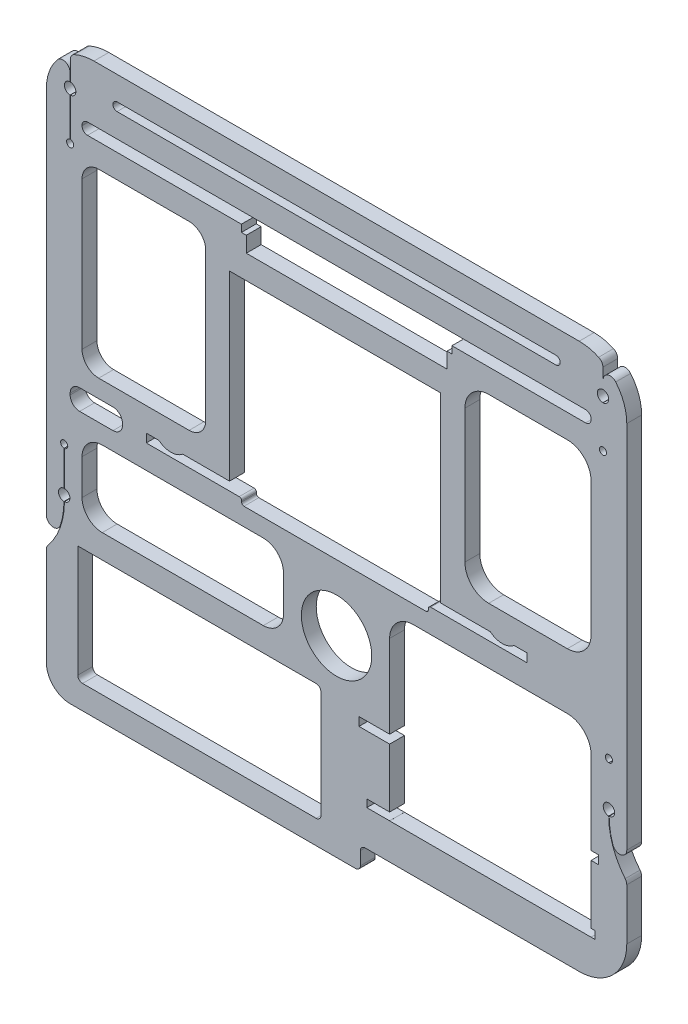
SolidWorks part; units mm, degrees
ref_plane "Front Plane" through (0, 0, 0) normal (0, 0, 1) x (1, 0, 0)
ref_plane "Top Plane" through (0, 0, 0) normal (0, 1, 0) x (1, 0, 0)
ref_plane "Right Plane" through (0, 0, 0) normal (1, 0, 0) x (0, 0, -1)
sketch "Sketch1" plane through (0, 0, 0) normal (0, 0, 1) x (1, 0, 0)
  line L0 (63.9883, 61.406) -> (63.9883, 57.596) construction
  line L1 (11.1776, 3.1158) -> (73.1542, 3.1158)
  line L2 (11.1776, 3.1158) -> (11.1776, 61.406)
  line L3 (11.1776, 61.406) -> (73.1542, 61.406)
  line L4 (73.1542, 3.1158) -> (73.1542, 61.406)
  line L5 (69.3442, 57.596) -> (14.9876, 57.596)
  line L6 (69.3442, 57.596) -> (69.3442, 6.9258)
  line L7 (69.3442, 6.9258) -> (14.9876, 6.9258)
  line L8 (14.9876, 57.596) -> (14.9876, 6.9258)
  line L9 (63.9883, 59.501) -> (18.0707, 59.501) construction
  line L10 (14.9876, 39.3805) -> (11.1776, 39.3805) construction
  line L11 (13.0826, 39.3805) -> (13.0826, 23.9527) construction
  line L12 (13.5248, 6.9258) -> (13.5248, 3.1158) construction
  line L13 (13.5248, 5.0208) -> (21.1598, 5.0208) construction
  line L14 (73.1542, 38.1916) -> (69.3442, 38.1916) construction
  line L15 (71.2492, 38.1916) -> (71.2492, 22.3321) construction
  line L16 (55.7422, 59.501) -> (30.5962, 59.501) construction
  line L19 (42.3087, 5.0208) -> (41.7626, 5.0208) construction
  line L21 (69.3442, 27.6227) -> (69.3442, 52.516) construction
  line L22 (14.9876, 47.563) -> (14.9876, 27.6227) construction
  dimension "D1" = 3.81
  dimension "D2" = 3.81
extrude "Boss-Extrude1" add sketch "Sketch1" along normal blind 1.5875
sketch "Sketch2" plane through (0, 0, 0) normal (0, 0, -1) x (-1, 0, 0)
  line L0 (-69.3442, 6.9258) -> (-69.3442, 57.596) construction
  line L1 (-69.3442, 28.8799) -> (-14.9876, 28.8799)
  line L2 (-69.3442, 28.8799) -> (-69.3442, 26.3399)
  line L3 (-69.3442, 26.3399) -> (-14.9876, 26.3399)
  line L4 (-14.9876, 28.8799) -> (-14.9876, 26.3399)
  line L5 (-14.9876, 57.596) -> (-14.9876, 6.9258) construction
  line L7 (-53.9642, 53.4304) -> (-53.9642, 51.7667)
  line L8 (-32.5266, 53.4304) -> (-32.0059, 53.4304)
  line L9 (-32.5266, 51.7667) -> (-53.9642, 51.7667) construction
  line L10 (-32.5266, 51.7667) -> (-32.5266, 53.4304) construction
  line L11 (-69.3442, 54.1924) -> (-54.4849, 54.1924)
  line L12 (-69.3442, 54.1924) -> (-69.3442, 51.6524)
  line L13 (-69.3442, 51.6524) -> (-55.8692, 51.6524)
  line L14 (-14.9876, 54.1924) -> (-14.9876, 51.6524)
  line L15 (-69.3442, 57.596) -> (-14.9876, 57.596)
  line L16 (-69.3442, 57.596) -> (-69.3442, 55.4243)
  line L17 (-69.3442, 55.4243) -> (-14.9876, 55.4243)
  line L18 (-14.9876, 57.596) -> (-14.9876, 55.4243)
  line L19 (-69.3442, 57.596) -> (-14.9876, 57.596) construction
  line L20 (-54.4849, 54.1924) -> (-54.4849, 53.4304)
  line L21 (-62.3462, 55.4243) -> (-23.9922, 55.4243) construction
  line L22 (-54.4849, 53.4304) -> (-53.9642, 53.4304)
  line L23 (-32.5266, 51.7667) -> (-53.9642, 51.7667)
  line L24 (-32.5266, 51.7667) -> (-32.5266, 53.4304)
  line L25 (-55.8692, 51.6524) -> (-55.8692, 49.2267)
  line L26 (-55.8692, 49.2267) -> (-30.6216, 49.2267)
  line L27 (-30.6216, 49.2267) -> (-30.6216, 51.6524)
  line L28 (-30.6216, 51.6524) -> (-14.9876, 51.6524)
  line L29 (-32.0059, 53.4304) -> (-32.0059, 54.1924)
  line L30 (-62.3462, 54.1924) -> (-23.9922, 54.1924) construction
  line L31 (-62.4859, 28.8799) -> (-21.8459, 28.8799) construction
  line L32 (-54.4849, 53.4304) -> (-54.4849, 54.1924) construction
  line L33 (-32.0059, 53.4304) -> (-54.4849, 53.4304) construction
  line L34 (-32.0059, 54.1924) -> (-14.9876, 54.1924)
  line L36 (-32.0059, 53.4304) -> (-32.0059, 54.1924) construction
  line L37 (-32.5266, 51.7667) -> (-32.5266, 53.4304) construction
  dimension "D1" = 2.54
  dimension "D2" = 1.905
  dimension "D3" = 2.54
  dimension "D4" = 1.905
  dimension "D5" = 2.54
extrude "Boss-Extrude2" add sketch "Sketch2" against normal up to surface (1.5875 mm away) up to face at (42.1659, 32.2609, 1.5875)
sketch "Sketch3" plane through (0, 0, 0) normal (0, 0, -1) x (-1, 0, 0)
  line L1 (-51.983, 32.3343) -> (-51.983, 29.7943) construction
  line L2 (-53.253, 29.7943) -> (-69.3442, 29.7943)
  line L3 (-69.3442, 28.8799) -> (-69.3442, 51.6524) construction
  line L4 (-69.3442, 29.7943) -> (-69.3442, 32.3343)
  line L5 (-69.3442, 32.3343) -> (-55.8692, 32.3343)
  line L7 (-53.253, 29.7943) -> (-53.253, 49.2267)
  line L8 (-55.8692, 49.2267) -> (-30.6216, 49.2267) construction
  line L9 (-53.253, 49.2267) -> (-55.8692, 49.2267)
  line L10 (-55.8692, 49.2267) -> (-55.8692, 32.3343)
  line L12 (-62.4859, 29.7943) -> (-21.8459, 29.7943) construction
  line L13 (-30.7359, 29.7943) -> (-14.9876, 29.7943)
  line L14 (-14.9876, 51.6524) -> (-14.9876, 28.8799) construction
  line L15 (-14.9876, 29.7943) -> (-14.9876, 32.3343)
  line L16 (-14.9876, 32.3343) -> (-28.1959, 32.3343)
  line L17 (-28.1959, 32.3343) -> (-28.1959, 51.6524)
  line L18 (-30.6216, 51.6524) -> (-14.9876, 51.6524) construction
  line L19 (-28.1959, 51.6524) -> (-30.7359, 51.6524)
  line L20 (-30.7359, 51.6524) -> (-30.7359, 29.7943)
  line L21 (-32.0059, 32.3343) -> (-32.0059, 29.7943) construction
  line L22 (-55.8692, 51.6524) -> (-55.8692, 49.2267) construction
  line M22 (-69.3442, 28.8799) -> (-69.3442, 51.6524)
  line M25 (-55.8692, 49.2267) -> (-30.6216, 49.2267)
  line M27 (-30.6216, 51.6524) -> (-14.9876, 51.6524)
  line M28 (-14.9876, 51.6524) -> (-14.9876, 28.8799)
  dimension "D1" = 2.54
  dimension "D3" = 2.54
  dimension "D4" = 2.54
  dimension "D5" = 1.27
  dimension "D6" = 1.27
extrude "Boss-Extrude3" add sketch "Sketch3" against normal up to surface (1.5875 mm away) contours L10 L5 L2 L7 M25 M22 | L20 L13 L16 L17 M27 M28 region at (30.4665, 50.4396, 0) region at (61.2986, 30.0466, 0) up to face at (42.8855, 53.7395, 1.5875)
sketch "Sketch4" plane through (0, 0, 0) normal (0, 0, -1) x (-1, 0, 0)
  line L0 (-69.3442, 26.3399) -> (-14.9876, 26.3399) construction
  line L1 (-47.8301, 26.3399) -> (-36.5017, 26.3399)
  line L2 (-47.8301, 26.3399) -> (-47.8301, 6.9258)
  line L3 (-47.8301, 6.9258) -> (-36.5017, 6.9258)
  line L4 (-36.5017, 26.3399) -> (-36.5017, 6.9258)
  line L5 (-14.9876, 6.9258) -> (-69.3442, 6.9258) construction
  line L6 (-45.9251, 21.2246) -> (-47.8301, 21.2246) construction
  line L7 (-38.4067, 21.2246) -> (-36.5017, 21.2246) construction
  circle A0 centre (-42.1659, 21.2246) radius 3.7592 construction
  dimension "D1" = 1.905
extrude "Boss-Extrude4" add sketch "Sketch4" against normal up to surface (1.5875 mm away) up to face at (21.5917, 41.9934, 1.5875)
sketch "Sketch5" plane through (0, 0, 0) normal (0, 0, -1) x (-1, 0, 0)
  line L0 (-14.5338, 15.7015) -> (-40.4926, 15.7015) construction
  line L3 (-40.4926, 3.2428) -> (-40.4926, 15.7015) construction
  line L4 (-14.5338, 3.2428) -> (-40.4926, 3.2428) construction
  line L5 (-14.5338, 3.2428) -> (-14.5338, 15.7015) construction
  line L6 (-14.5338, 15.7015) -> (-40.4926, 15.7015)
  line L7 (-40.4926, 3.2428) -> (-40.4926, 15.7015)
  line L8 (-14.5338, 3.2428) -> (-40.4926, 3.2428)
  line L9 (-14.5338, 3.2428) -> (-14.5338, 15.7015)
  circle A0 centre (-42.1659, 21.2246) radius 3.7592 construction
  circle A1 centre (-42.1659, 21.2246) radius 3.7592
extrude "Cut-Extrude1" cut sketch "Sketch5" against normal up to surface (1.5875 mm away) up to face at (58.5871, 16.6329, 1.5875)
sketch "Sketch8" plane through (0, 0, 0) normal (0, 0, -1) x (-1, 0, 0)
  line L1 (-36.5017, 15.7015) -> (-14.9876, 15.7015)
  line L2 (-36.5017, 15.7015) -> (-36.5017, 18.2415)
  line L3 (-36.5017, 18.2415) -> (-14.9876, 18.2415)
  line L4 (-14.9876, 15.7015) -> (-14.9876, 18.2415)
  line L5 (-14.9876, 26.3399) -> (-14.9876, 15.7015) construction
  dimension "D1" = 2.54
extrude "Boss-Extrude5" add sketch "Sketch8" against normal up to surface (1.5875 mm away) up to face at (38.4067, 21.2246, 1.5875)
fillet "Fillet1" radius 5.08 3 edges at (73.1542, 3.1158, 0.7937) (11.1776, 61.406, 0.7937) (73.1542, 61.406, 0.7937)
fillet "Fillet2" radius 2.54 4 edges at (69.3442, 51.6524, 0.7937) (55.8692, 32.3343, 0.7937) (69.3442, 32.3343, 0.7937) (55.8692, 51.6524, 0.7937)
fillet "Fillet3" radius 1.778 4 edges at (14.9876, 32.3343, 0.7937) (28.1959, 32.3343, 0.7937) (14.9876, 51.6524, 0.7937) (28.1959, 51.6524, 0.7937)
fillet "Fillet4" radius 0.5842 4 edges at (14.9876, 55.4243, 0.7937) (69.3442, 55.4243, 0.7937) (69.3442, 54.1924, 0.7937) (14.9876, 54.1924, 0.7937)
fillet "Fillet8" radius 2.159 4 edges at (36.5017, 18.2415, 0.7937) (36.5017, 26.3399, 0.7937) (14.9876, 26.3399, 0.7937) (14.9876, 18.2415, 0.7937)
sketch "Sketch6" plane through (0, 0, 0) normal (0, 0, -1) x (-1, 0, 0)
  circle A0 centre (-71.2492, 19.6852) radius 0.6096 construction
  circle A1 centre (-71.2492, 19.6852) radius 0.6096
  circle A4 centre (-70.6142, 57.596) radius 0.6096 construction
  circle A5 centre (-70.6142, 57.596) radius 0.6096
  circle A6 centre (-13.0826, 19.6852) radius 0.6096 construction
  circle A7 centre (-13.0826, 19.6852) radius 0.6096
  circle A10 centre (-13.7176, 57.596) radius 0.6096 construction
  circle A11 centre (-13.7176, 57.596) radius 0.6096
extrude "Cut-Extrude2" cut sketch "Sketch6" against normal up to surface (1.5875 mm away) up to face at (27.5132, 9.4722, 1.5875)
sketch "Sketch7" plane through (0, 0, 0) normal (0, 0, -1) x (-1, 0, 0)
  line L0 (-44.5566, 14.9395) -> (-70.1344, 14.9395) construction
  line L1 (-70.1344, 14.9395) -> (-70.1344, 14.0251) construction
  line L2 (-70.1344, 14.0251) -> (-44.5566, 14.0251) construction
  line L3 (-44.5566, 14.0251) -> (-44.5566, 14.9395) construction
  line L4 (-45.3906, 7.7431) -> (-69.7746, 7.7431) construction
  line L5 (-69.7746, 7.7431) -> (-69.7746, 6.9303) construction
  line L6 (-69.7746, 6.9303) -> (-45.3906, 6.9303) construction
  line L7 (-45.3906, 6.9303) -> (-45.3906, 7.7431) construction
  line L8 (-44.5566, 14.9395) -> (-70.1344, 14.9395)
  line L9 (-70.1344, 14.9395) -> (-70.1344, 14.0251)
  line L10 (-70.1344, 14.0251) -> (-44.5566, 14.0251)
  line L11 (-44.5566, 14.0251) -> (-44.5566, 14.9395)
  line L12 (-45.3906, 7.7431) -> (-69.7746, 7.7431)
  line L13 (-69.7746, 7.7431) -> (-69.7746, 6.9303)
  line L14 (-69.7746, 6.9303) -> (-45.3906, 6.9303)
  line L15 (-45.3906, 6.9303) -> (-45.3906, 7.7431)
  line L20 (-67.1076, 7.7431) -> (-48.0576, 7.7431)
  line L21 (-48.0576, 7.7431) -> (-48.0576, 9.6227)
  line L22 (-48.0576, 9.6227) -> (-67.1076, 9.6227)
  line L23 (-67.1076, 9.6227) -> (-67.1076, 7.7431)
  line L24 (-67.1076, 7.7431) -> (-48.0576, 7.7431)
  line L25 (-48.0576, 7.7431) -> (-48.0576, 9.6227)
  line L26 (-48.0576, 9.6227) -> (-67.1076, 9.6227)
  line L27 (-67.1076, 9.6227) -> (-67.1076, 7.7431)
  dimension "D1" = 0
extrude "Cut-Extrude3" cut sketch "Sketch7" against normal up to surface (1.5875 mm away) contours L14 L15 L12 L13 | L26 L27 L12 L25 | L10 L11 L8 L9 region at (57.3455, 14.4823, 0) region at (57.5826, 7.3367, 0) region at (57.5826, 8.6829, 0) up to face at (13.108, 57.596, 1.5875)
fillet "Fillet6" radius 0.508 3 edges at (40.4926, 15.7015, 0.7937) (40.4926, 3.2428, 0.7937) (14.5338, 3.2428, 0.7937)
sketch "Sketch9" plane through (0, 0, 1.5875) normal (0, 0, 1) x (1, 0, 0)
  line L0 (68.0742, 61.406) -> (16.2576, 61.406) construction
  line L1 (18.2896, 58.866) -> (66.0422, 58.866)
  line L2 (18.2896, 58.866) -> (18.2896, 57.9643)
  line L3 (18.2896, 57.9643) -> (66.0422, 57.9643)
  line L8 (66.0422, 58.866) -> (66.0422, 57.9643)
  line L9 (15.5718, 55.4243) -> (68.76, 55.4243) construction
  line L10 (11.1776, 56.326) -> (11.1776, 59.3208) construction
  line L11 (18.2896, 58.866) -> (11.1776, 58.866) construction
  line L13 (66.0422, 58.866) -> (73.1542, 58.866) construction
  line L14 (73.1542, 56.326) -> (73.1542, 56.8419) construction
  dimension "D1" = 2.54
  dimension "D2" = 2.54
  dimension "D3" = 7.112
extrude "Cut-Extrude4" cut sketch "Sketch9" against normal up to surface (1.5875 mm away) up to face at (58.1379, 12.0542, 0)
fillet "Fillet7" radius 0.4318 4 edges at (18.2896, 57.9643, 0.7937) (18.2896, 58.866, 0.7937) (66.0422, 57.9643, 0.7937) (66.0422, 58.866, 0.7937)
fillet "Fillet9" radius 2.54 2 edges at (69.3442, 26.3399, 0.7937) (47.8301, 26.3399, 0.7937)
sketch "Sketch10" plane through (0, 0, 1.5875) normal (0, 0, 1) x (1, 0, 0)
  line L0 (42.1659, 24.9838) -> (42.1659, -13.4858) construction
  line L1 (11.1776, 3.1158) -> (44.7059, 3.1158)
  line L2 (11.1776, 3.1158) -> (11.1776, 0.7028)
  line L3 (11.1776, 0.7028) -> (44.7059, 0.7028)
  line L4 (44.7059, 3.1158) -> (44.7059, 0.7028)
  line L5 (15.0418, 3.2428) -> (39.9846, 3.2428) construction
  circle A0 centre (42.1659, 21.2246) radius 3.7592 construction
  dimension "D1" = 2.54
  dimension "D2" = 2.54
extrude "Boss-Extrude6" add sketch "Sketch10" against normal up to surface (1.5875 mm away) up to face at (42.1659, 58.4152, 0)
fillet "Fillet10" radius 2.54 1 edges at (11.1776, 0.7028, 0.7937)
fillet "Fillet11" radius 0.508 2 edges at (44.7059, 3.1158, 0.7937) (44.7059, 0.7028, 0.7937)
sketch "Sketch11" plane through (0, 0, 1.5875) normal (0, 0, 1) x (1, 0, 0)
  line L0 (13.7049, 59.0933) -> (13.7049, 58.2055) construction
  line L1 (13.7049, 56.9866) -> (13.7049, 52.8968) construction
  line L2 (13.7303, 52.8968) -> (13.7303, 56.9866) construction
  line L3 (13.7303, 58.2055) -> (13.7303, 60.2667) construction
  line L4 (70.6015, 58.2055) -> (70.6015, 60.2667) construction
  line L5 (70.6269, 56.9866) -> (70.6269, 52.8968) construction
  line L6 (70.6015, 52.8968) -> (70.6015, 56.9866) construction
  line L7 (71.2619, 24.0038) -> (71.2619, 20.2947) construction
  line L8 (71.2365, 24.0038) -> (71.2365, 20.2947) construction
  line L9 (13.0953, 24.0038) -> (13.0953, 20.2947) construction
  line L10 (13.0699, 24.0038) -> (13.0699, 20.2947) construction
  line L11 (13.7049, 59.0933) -> (13.7049, 58.2055)
  line L12 (13.7049, 56.9866) -> (13.7049, 52.8968)
  line L13 (13.7303, 52.8968) -> (13.7303, 56.9866)
  line L14 (13.7303, 58.2055) -> (13.7303, 60.2667)
  line L15 (70.6015, 58.2055) -> (70.6015, 60.2667)
  line L16 (70.6269, 56.9866) -> (70.6269, 52.8968)
  line L17 (70.6015, 52.8968) -> (70.6015, 56.9866)
  line L18 (71.2619, 24.0038) -> (71.2619, 20.2947)
  line L19 (71.2365, 24.0038) -> (71.2365, 20.2947)
  line L20 (13.0953, 24.0038) -> (13.0953, 20.2947)
  line L21 (13.0699, 24.0038) -> (13.0699, 20.2947)
  line L22 (73.1542, 8.1958) -> (73.1542, 56.326) construction
  line L23 (11.1776, 56.326) -> (11.1776, 3.2428) construction
  line L24 (73.1542, 13.6774) -> (73.1542, 16.8829)
  line L25 (11.1776, 16.8829) -> (11.1776, 13.6774)
  line L26 (70.6269, 59.0933) -> (70.6269, 58.2055) construction
  line L27 (70.6269, 59.0933) -> (70.6269, 58.2055)
  arc A0 (13.7049, 59.0933) -> (12.3579, 59.5817) centre (12.9429, 59.0933) ccw construction
  arc A1 (13.7049, 52.8968) -> (13.7303, 52.8968) centre (13.7176, 52.516) ccw construction
  arc A2 (14.1807, 60.9621) -> (13.7303, 60.2667) centre (14.4923, 60.2667) ccw construction
  arc A3 (70.6015, 60.2667) -> (70.151, 60.9621) centre (69.8395, 60.2667) ccw construction
  arc A4 (71.9738, 59.5817) -> (70.6269, 59.0933) centre (71.3889, 59.0933) ccw construction
  arc A5 (70.6015, 52.8968) -> (70.6269, 52.8968) centre (70.6142, 52.516) ccw construction
  arc A6 (71.2619, 24.0038) -> (71.2365, 24.0038) centre (71.2492, 24.3846) ccw construction
  arc A7 (71.2746, 19.0762) -> (71.6692, 16.6421) centre (78.975, 19.0756) ccw construction
  arc A8 (71.6692, 16.6421) -> (73.1542, 16.8829) centre (72.3922, 16.8829) ccw construction
  arc A9 (71.2238, 19.0762) -> (72.9814, 14.1605) centre (78.975, 19.0756) ccw construction
  arc A10 (73.1542, 13.6774) -> (72.9814, 14.1605) centre (72.3922, 13.6774) ccw construction
  arc A11 (13.0953, 24.0038) -> (13.0699, 24.0038) centre (13.0826, 24.3846) ccw construction
  arc A12 (11.3503, 14.1605) -> (13.108, 19.0762) centre (5.3567, 19.0756) ccw construction
  arc A13 (12.6625, 16.6421) -> (13.0572, 19.0762) centre (5.3567, 19.0756) ccw construction
  arc A14 (11.1776, 16.8829) -> (12.6625, 16.6421) centre (11.9396, 16.8829) ccw construction
  arc A15 (11.3503, 14.1605) -> (11.1776, 13.6774) centre (11.9396, 13.6774) ccw construction
  arc A16 (13.7049, 59.0933) -> (12.3579, 59.5817) centre (12.9429, 59.0933) ccw
  arc A17 (13.7049, 52.8968) -> (13.7303, 52.8968) centre (13.7176, 52.516) ccw
  arc A18 (14.1807, 60.9621) -> (13.7303, 60.2667) centre (14.4923, 60.2667) ccw
  arc A19 (70.6015, 60.2667) -> (70.151, 60.9621) centre (69.8395, 60.2667) ccw
  arc A20 (71.9738, 59.5817) -> (70.6269, 59.0933) centre (71.3889, 59.0933) ccw
  arc A21 (70.6015, 52.8968) -> (70.6269, 52.8968) centre (70.6142, 52.516) ccw
  arc A22 (71.2619, 24.0038) -> (71.2365, 24.0038) centre (71.2492, 24.3846) ccw
  arc A23 (71.2746, 19.0762) -> (71.6692, 16.6421) centre (78.975, 19.0756) ccw
  arc A24 (71.6692, 16.6421) -> (73.1542, 16.8829) centre (72.3922, 16.8829) ccw
  arc A25 (71.2238, 19.0762) -> (72.9814, 14.1605) centre (78.975, 19.0756) ccw
  arc A26 (73.1542, 13.6774) -> (72.9814, 14.1605) centre (72.3922, 13.6774) ccw
  arc A27 (13.0953, 24.0038) -> (13.0699, 24.0038) centre (13.0826, 24.3846) ccw
  arc A28 (11.3503, 14.1605) -> (13.108, 19.0762) centre (5.3567, 19.0756) ccw
  arc A29 (12.6625, 16.6421) -> (13.0572, 19.0762) centre (5.3567, 19.0756) ccw
  arc A30 (11.1776, 16.8829) -> (12.6625, 16.6421) centre (11.9396, 16.8829) ccw
  arc A31 (11.3503, 14.1605) -> (11.1776, 13.6774) centre (11.9396, 13.6774) ccw
  arc A32 (16.2576, 61.406) -> (11.1776, 56.326) centre (16.2576, 56.326) ccw construction
  circle A33 centre (13.7176, 57.596) radius 0.6096 construction
  arc A34 (73.1542, 56.326) -> (68.0742, 61.406) centre (68.0742, 56.326) ccw construction
  circle A35 centre (70.6142, 57.596) radius 0.6096 construction
  circle A36 centre (71.2492, 19.6852) radius 0.6096 construction
  circle A37 centre (13.0826, 19.6852) radius 0.6096 construction
  arc A38 (14.1807, 60.9621) -> (12.3579, 59.5817) centre (16.2576, 56.326) ccw
  arc A39 (13.7303, 58.2055) -> (13.7049, 58.2055) centre (13.7176, 57.596) ccw
  arc A40 (71.9738, 59.5817) -> (70.151, 60.9621) centre (68.0742, 56.326) ccw
  arc A41 (70.6015, 56.9866) -> (70.6269, 56.9866) centre (70.6142, 57.596) ccw
  arc A42 (71.2619, 20.2947) -> (71.2365, 20.2947) centre (71.2492, 19.6852) ccw
  arc A43 (13.0572, 19.0762) -> (13.108, 19.0762) centre (13.0826, 19.6852) ccw
  arc A44 (13.0953, 20.2947) -> (13.0699, 20.2947) centre (13.0826, 19.6852) ccw
  arc A45 (13.7049, 56.9866) -> (13.7303, 56.9866) centre (13.7176, 57.596) ccw
  arc A46 (71.2238, 19.0762) -> (71.2746, 19.0762) centre (71.2492, 19.6852) ccw
  arc A47 (70.6015, 56.9866) -> (70.6269, 56.9866) centre (70.6142, 57.596) ccw
  arc A48 (70.6269, 58.2055) -> (70.6015, 58.2055) centre (70.6142, 57.596) ccw
extrude "Cut-Extrude5" cut sketch "Sketch11" against normal through all contours A39 L14 A18 A38 A16 L11 | A45 L12 A17 L13 | A43 A29 A30 L25 A31 A28 | A44 L20 A27 L21 | A46 A25 A26 L24 A24 A23 | A42 L18 A22 L19 | A48 L27 A20 A40 A19 L15 | A41 L17 A21 L16 region at (13.3996, 60.0409, 1.5875) region at (13.7176, 52.9661, 1.5875) region at (70.9321, 60.0409, 1.5875) region at (70.6142, 52.9661, 1.5875) region at (71.2492, 24.0019, 1.5875) region at (13.0826, 24.0019, 1.5875) region at (72.5827, 15.6068, 1.5875) region at (11.749, 15.6068, 1.5875)
sketch "Sketch12" plane through (0, 0, 0) normal (0, 0, -1) x (-1, 0, 0)
  line L0 (-30.7359, 29.7943) -> (-14.9876, 29.7943) construction
  line L1 (-22.8238, 29.7943) -> (-26.1258, 29.7943) construction
  line L2 (-22.8238, 29.7943) -> (-23.2048, 29.7943) construction
  line L3 (-25.7448, 29.7943) -> (-26.1258, 29.7943) construction
  line L4 (-24.4748, 29.3371) -> (-24.4748, 29.7943) construction
  line L5 (-24.4748, 28.8799) -> (-24.4748, 29.7943) construction
  line L6 (-24.4748, 29.3371) -> (-24.4748, 28.8799) construction
  line L7 (-14.9876, 28.8799) -> (-69.3442, 28.8799) construction
  line L8 (-25.7933, 29.7943) -> (-23.2048, 29.7943)
  line L9 (-58.206, 29.7943) -> (-61.508, 29.7943) construction
  line L10 (-58.206, 29.7943) -> (-58.587, 29.7943) construction
  line L11 (-61.127, 29.7943) -> (-61.508, 29.7943) construction
  line L12 (-59.857, 29.3371) -> (-59.857, 28.8799) construction
  line L13 (-61.508, 28.8799) -> (-58.206, 28.8799) construction
  line L14 (-59.857, 29.3371) -> (-59.857, 29.7943) construction
  line L15 (-53.253, 29.7943) -> (-69.3442, 29.7943) construction
  line L16 (-59.857, 28.8799) -> (-59.857, 29.7943) construction
  line L17 (-61.127, 29.7943) -> (-58.587, 29.7943)
  arc A0 (-25.7448, 29.7943) -> (-23.2048, 29.7943) centre (-24.4748, 31.3296) ccw
  arc A1 (-61.127, 29.7943) -> (-58.587, 29.7943) centre (-59.857, 31.3296) ccw
  dimension "D1" = 0.381
extrude "Boss-Extrude7" add sketch "Sketch12" against normal up to surface (1.5875 mm away) contours L8 A0 | L17 A1 region at (24.4748, 29.6095, 0) region at (59.857, 29.6095, 0) up to face at (25.7446, 22.2907, 1.5875)
sketch "Sketch13" plane through (0, 0, 0) normal (0, 0, -1) x (-1, 0, 0)
  line L0 (-62.4859, 29.7943) -> (-62.4859, 28.8799) construction
  line L1 (-62.4859, 29.7943) -> (-62.4859, 28.8799)
  line L2 (-61.127, 29.7943) -> (-69.3442, 29.7943) construction
  line L3 (-69.3442, 28.8799) -> (-69.3442, 29.7943) construction
  line L4 (-14.9876, 28.8799) -> (-69.3442, 28.8799) construction
  line L5 (-62.4859, 29.7943) -> (-69.3442, 29.7943)
  line L6 (-69.3442, 28.8799) -> (-69.3442, 29.7943)
  line L7 (-62.4859, 28.8799) -> (-69.3442, 28.8799)
  line L8 (-21.8459, 29.7943) -> (-21.8459, 28.8799) construction
  line L9 (-21.8459, 29.7943) -> (-21.8459, 28.8799)
  line L10 (-14.9876, 29.7943) -> (-14.9876, 28.8799) construction
  line L11 (-23.2048, 29.7943) -> (-14.9876, 29.7943) construction
  line L12 (-14.9876, 28.8799) -> (-21.8459, 28.8799)
  line L13 (-14.9876, 29.7943) -> (-14.9876, 28.8799)
  line L14 (-21.8459, 29.7943) -> (-14.9876, 29.7943)
  line L15 (-62.4859, 28.8799) -> (-69.3442, 28.8799)
extrude "Boss-Extrude8" add sketch "Sketch13" against normal up to surface (1.5875 mm away) contours L14 L9 L12 L13 | L7 L1 L5 L6 region at (65.915, 29.3371, 0) region at (18.4167, 29.3371, 0) up to face at (25.7446, 22.2907, 1.5875)
sketch "Sketch14" plane through (0, 0, 0) normal (0, 0, -1) x (-1, 0, 0)
  line L0 (-21.8459, 29.3371) -> (-19.3059, 29.3371) construction
  line L1 (-19.3059, 30.4293) -> (-13.7176, 30.4293)
  line L2 (-19.3059, 30.4293) -> (-19.3059, 28.2449)
  line L3 (-19.3059, 28.2449) -> (-13.7176, 28.2449)
  line L4 (-13.7176, 30.4293) -> (-13.7176, 28.2449)
  line L5 (-21.8459, 29.7943) -> (-21.8459, 28.8799) construction
  line L6 (-13.7176, 29.3371) -> (-11.1776, 29.3371) construction
  line L7 (-11.1776, 56.326) -> (-11.1776, 16.8829) construction
  line L8 (-18.0489, 32.3343) -> (-18.0489, 30.4293) construction
  line L9 (-16.7656, 32.3343) -> (-26.4179, 32.3343) construction
  line L11 (-18.0489, 28.2449) -> (-18.0489, 26.3399) construction
  line L12 (-34.3427, 26.3399) -> (-17.1466, 26.3399) construction
  point P4 (-19.3059, 29.3371)
  dimension "D1" = 2.54
  dimension "D2" = 1.905
extrude "Cut-Extrude6" cut sketch "Sketch14" against normal through all
fillet "Fillet12" radius 1.016 4 edges at (13.7176, 30.4293, 0.7938) (13.7176, 28.2449, 0.7937) (19.3059, 28.2449, 0.7938) (19.3059, 30.4293, 0.7938)
sketch "Sketch15" plane through (0, 0, 0) normal (0, 0, -1) x (-1, 0, 0)
  line L0 (-21.8459, 28.8799) -> (-62.4859, 28.8799) construction
  line L1 (-51.9639, 28.8799) -> (-32.0249, 28.8799)
  line L2 (-51.9639, 28.8799) -> (-51.9639, 28.2449)
  line L3 (-51.9639, 28.2449) -> (-32.0249, 28.2449)
  line L4 (-32.0249, 28.8799) -> (-32.0249, 28.2449)
  line L5 (-51.2019, 26.7844) -> (-51.2019, 28.8799) construction
  line L6 (-32.7869, 26.7844) -> (-32.7869, 28.8799) construction
  dimension "D1" = 0.762
  dimension "D2" = 0.635
  dimension "D3" = 0.762
extrude "Cut-Extrude7" cut sketch "Sketch15" against normal through all
fillet "Fillet13" radius 0.254 4 edges at (32.0249, 28.2449, 0.7938) (32.0249, 28.8799, 0.7938) (51.9639, 28.2449, 0.7938) (51.9639, 28.8799, 0.7938)
